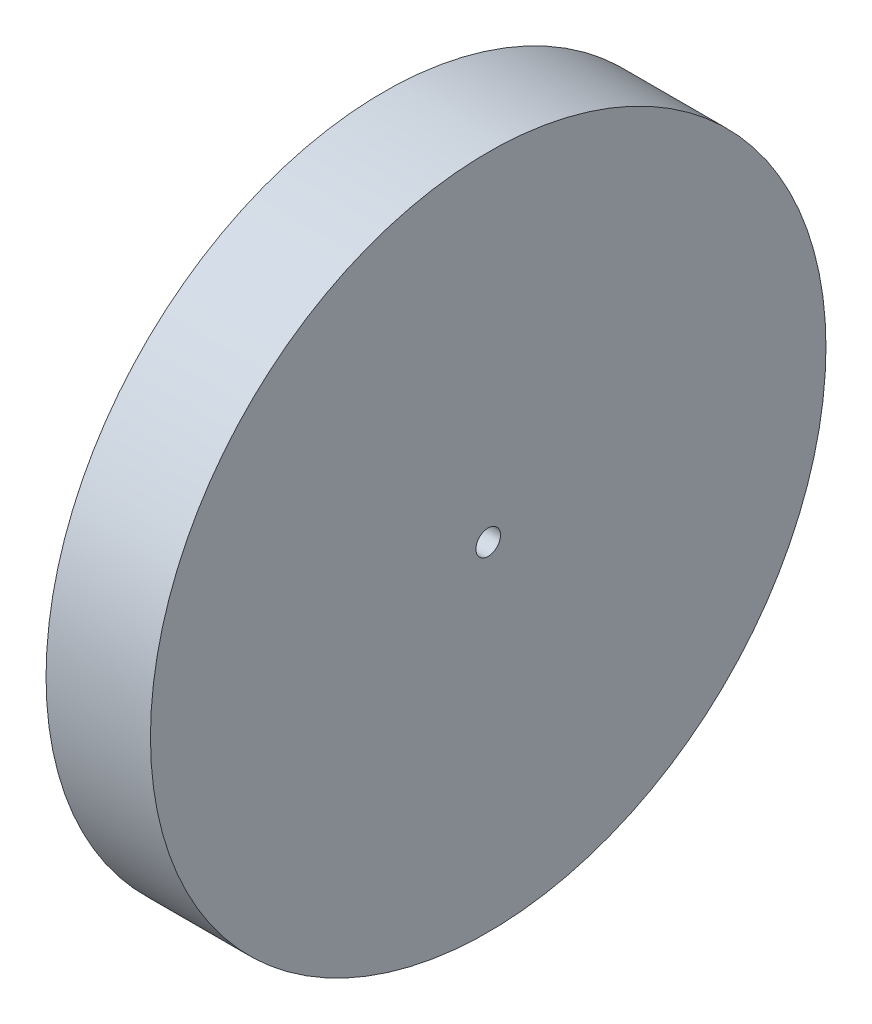
SolidWorks part; units mm, degrees
ref_plane "Plane1" through (0, 0, 0) normal (0, 0, 1) x (1, 0, 0)
ref_plane "Plane2" through (0, 0, 0) normal (0, 1, 0) x (1, 0, 0)
ref_plane "Plane3" through (0, 0, 0) normal (1, 0, 0) x (0, 0, -1)
sketch "HoldingSke" plane through (0, 0, 0) normal (0, 1, 0) x (1, 0, 0)
  line L0 (0, 0) -> (0.3214, -0.383)
  line L1 (-15, 0) -> (100, 0) construction
  line L2 (0, 0) -> (-2.1039, 2.3779)
  line L3 (0, 0) -> (-11.863, 4.5341)
  line L4 (0, 0) -> (5.5511, 6.6156)
  line L5 (0, 0) -> (-23.7986, -8.8762)
  line L6 (0, 0) -> (-10.5278, -7.1032)
  line L7 (-2.1039, 2.3779) -> (3.3635, 27.1825)
  line L8 (-76.2, 4.3779) -> (-54.61, 4.3779)
  line L9 (-71.009, 38.7566) -> (-53.1078, 45.2721)
  line L10 (-76.2, 71.12) -> (104.1128, 71.12)
  line L11 (0, 0) -> (-12, 0)
  line L12 (-76.2, 101.6) -> (-76.133, 101.6)
  line L13 (24.9733, 27.94) -> (52.9518, 28.4284)
  line L14 (24.9733, 27.94) -> (24.9743, 27.94)
  line L15 (24.9733, 27.94) -> (100.4006, 29.5858)
  circle A0 centre (0, 0) radius 60
  circle A1 centre (0, 0) radius 12.7
  circle A2 centre (0, 0) radius 12.7
  dimension "MHD" = 25.4
  dimension "Hub_dia" = 25.4
  dimension "Diameter" = 120
  dimension "Num_teeth" = 50
  dimension "Pitch_radius" = 180.3128
  dimension "Pitch" = 0.5
  dimension "Width" = 12
  dimension "Overall_len" = 25.4
  dimension "Show_teeth" = 50
  dimension "Thickness" = 12.7
  dimension "OAL" = 25.4001
  dimension "T_dim" = 21.59
  dimension "Ap" = 20
  dimension "H" = 19.05
  dimension "Backlash" = 0.067
  dimension "Addendum_fac" = 1
  dimension "Dedendum_fac" = 1.25
  dimension "Clearance_fac" = 0.25
  dimension "Dedendum_add" = 0.001
  dimension "Module" = 2
sketch "BasProSke" plane through (0, 0, 0) normal (0, 1, 0) x (1, 0, 0)
  line L0 (-10, 0) -> (60, 0) construction
  line L1 (0, 48) -> (0, 60)
  line L2 (0, 48) -> (12, 48)
  line L3 (12, 48) -> (12, 60)
  line L4 (12, 60) -> (0, 60)
  dimension "Diameter" = 120
  dimension "Thickness" = 12
  dimension "Inside_diameter" = 96
revolve "Base-Revolve" add sketch "BasProSke" angle 360 about L0
sketch "TooCutSke" plane through (0, 0, 0) normal (1, 0, 0) x (0, 0, -1)
  line L3 (1.738, 49.9698) -> (1.738, 53.6633) construction
  line L4 (0, 0) -> (0, 59.563) construction
  line L5 (0, 0) -> (-4.2903, 68.1927) construction
  line L6 (-21.6015, 41.0107) -> (35.113, 44.5789) construction
  circle A0 centre (0, 0) radius 50 construction
  circle A1 centre (0, 0) radius 52.501 construction
  circle A2 centre (0, 0) radius 42.2862 construction
  circle A3 centre (0, 0) radius 47.9746 construction
  arc A4 (2.4267, 47.9132) -> (0.6033, 52.4975) centre (-21.6015, 41.0107) ccw
  arc A5 (2.4267, 47.9132) -> (-2.4267, 47.9132) centre (0, 0) ccw
  arc A6 (0.6033, 52.4975) -> (-0.6033, 52.4975) centre (0, 0) ccw
  arc A7 (-0.6033, 52.4975) -> (-2.4267, 47.9132) centre (21.6015, 41.0107) ccw
  dimension "Pitch_dia" = 100
  dimension "Base_dia" = 84.5723
  dimension "Root_dia" = 105.002
  dimension "Overcut_dia" = 95.9492
  dimension "Flank_rad" = 25
  dimension "Half_ang" = 3.6
  dimension "Half_CT" = 1.738
extrude "ToothCut" cut sketch "TooCutSke" along normal through all
fillet "Breaks" [suppressed] radius 0.2
fillet "RootFillets" [suppressed] radius 0.501
pattern_circular "TeethCuts" count 50 over 360 about axis through (-10, 0, 0) along (1, 0, 0) of "RootFillets", "Breaks", "ToothCut"
sketch "Esquisse1" plane through (12, 0, 0) normal (1, 0, 0) x (0, 0, -1)
  circle A0 centre (0, 0) radius 60
  circle A1 centre (0, 0) radius 2
  dimension "D1" = 120
  dimension "D2" = 4
extrude "Boss.-Extru.1" add sketch "Esquisse1" along normal blind 5
sketch "Esquisse2" plane through (17, 0, 0) normal (1, 0, 0) x (0, 0, -1)
  circle A0 centre (0, 0) radius 60
  circle A1 centre (0, 0) radius 55
  dimension "D1" = 5
  dimension "D2" = 120
extrude "Enlèv. mat.-Extru.1" cut sketch "Esquisse2" against normal up to next
equation "' \"Module@HoldingSke\" = 6.35"
equation "' \"Num_teeth@HoldingSke\" = 24"
equation "' \"Ap@HoldingSke\" =  14.5"
equation "' \"Width@HoldingSke\" = 12"
equation "' \"Diameter@HoldingSke\" = 8 * 25.4"
equation "' \"Show_teeth@HoldingSke\" = 100"
equation "' \"Backlash@HoldingSke\" = 0.009 * 25.4"
equation "' \"Addendum_fac@HoldingSke\" = 1.0"
equation "' \"Dedendum_fac@HoldingSke\" = 1.25"
equation "' \"Dedendum_add@HoldingSke\" = 0.00005 * 25.4"
equation "' \"Clearance_fac@HoldingSke\" = 0.25"
equation "\"Pitch@HoldingSke\" = 1 / \"Module@HoldingSke\" "
equation "\"Overcut_dia@TooCutSke\" = (\"Num_teeth@HoldingSke\" - 2 * \"Addendum_fac@HoldingSke\") / \"Pitch@HoldingSke\" - 0.002 * 25.4"
equation "\"Pitch_dia@TooCutSke\" = \"Num_teeth@HoldingSke\" / \"Pitch@HoldingSke\""
equation "\"Base_dia@TooCutSke\" = \"Num_teeth@HoldingSke\" / \"Pitch@HoldingSke\" * cos((\"Ap@HoldingSke\"  * 3.14159265 / 180)) * 0.90"
equation "\"Root_dia@TooCutSke\" = \"Num_teeth@HoldingSke\"  / \"Pitch@HoldingSke\" + 2 *  \"Dedendum_fac@HoldingSke\"/ \"Pitch@HoldingSke\" + \"Dedendum_add@HoldingSke\" * 2"
equation "\"Half_ang@TooCutSke\" = 180 / \"Num_teeth@HoldingSke\""
equation "\"Half_CT@TooCutSke\" = \"Num_teeth@HoldingSke\" / \"Pitch@HoldingSke\" * sin((3.14159265 / 2 / \"Num_teeth@HoldingSke\")) / 2 + 10 * \"Backlash@HoldingSke\" / 4"
equation "\"Flank_rad@TooCutSke\" = \"Num_teeth@HoldingSke\" / \"Pitch@HoldingSke\" / 4"
equation "\"Radius@RootFillets\"= \"Clearance_fac@HoldingSke\" / \"Pitch@HoldingSke\" + \"Dedendum_add@HoldingSke\""
equation "\"Break_rad@Breaks\" = 0.02 / \"Pitch@HoldingSke\" * 5"
equation "\"Num_teeth@TeethCuts\" = int( \"Show_teeth@HoldingSke\" ) + 1"
equation "\"Num_teeth@TeethCuts\" = ((sgn( \"Num_teeth@TeethCuts\" - \"Num_teeth@HoldingSke\" )-1)*( \"Num_teeth@TeethCuts\" - \"Num_teeth@HoldingSke\" ))/-2+ \"Num_teeth@HoldingSke\""
equation "\"Num_teeth@TeethCuts\" = ((sgn( \"Num_teeth@TeethCuts\" - 2.0)+1)*( \"Num_teeth@TeethCuts\" - 2.0))/2 +2.0"
equation "\"Angle@TeethCuts\" = 360.0 / \"Num_teeth@HoldingSke\""
equation "\"Diameter@BasProSke\" = \"Num_teeth@HoldingSke\"  / \"Pitch@HoldingSke\" + 2 *  \"Dedendum_fac@HoldingSke\"/ \"Pitch@HoldingSke\" + \"Dedendum_add@HoldingSke\" * 2 + 0.002 * 25.4"
equation "\"Diameter@BasProSke\" = ((sgn( \"Diameter@BasProSke\"  - \"Diameter@HoldingSke\" )+1)*( \"Diameter@BasProSke\"  - \"Diameter@HoldingSke\" ))/2 + \"Diameter@HoldingSke\""
equation "\"Inside_diameter@BasProSke\" =  (\"Num_teeth@HoldingSke\" - 2 * \"Addendum_fac@HoldingSke\") / \"Pitch@HoldingSke\" "
equation "\"Thickness@BasProSke\"  = \"Width@HoldingSke\""
